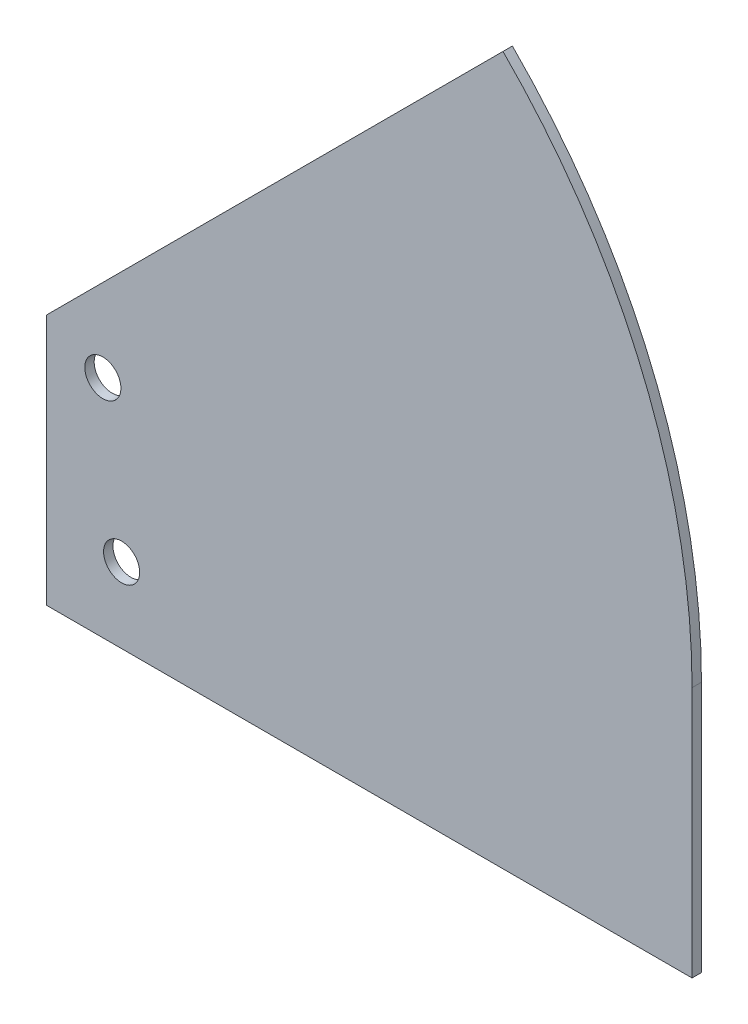
SolidWorks part; units mm, degrees
ref_plane "Front Plane" through (0, 0, 0) normal (0, 0, 1) x (1, 0, 0)
ref_plane "Top Plane" through (0, 0, 0) normal (0, 1, 0) x (1, 0, 0)
ref_plane "Right Plane" through (0, 0, 0) normal (1, 0, 0) x (0, 0, -1)
sketch "Sketch1" plane through (0, 0, 0) normal (0, 0, 1) x (1, 0, 0)
  line L0 (0, 0) -> (218.44, 0)
  line L2 (0, 85.09) -> (0, 0)
  line L3 (19.05, 76.2) -> (69.85, 76.2) construction
  line L4 (218.44, 0) -> (218.44, 85.09)
  line L7 (154.4604, 239.5504) -> (0, 85.09)
  line L8 (0, 85.09) -> (218.44, 85.09) construction
  line L9 (0, 303.53) -> (0, 85.09) construction
  circle A1 centre (19.05, 76.2) radius 6.1087
  circle A3 centre (19.05, 76.2) radius 50.8 construction
  arc A6 (0, 303.53) -> (154.4604, 239.5504) centre (0, 85.09) cw construction
  arc A7 (154.4604, 239.5504) -> (218.44, 85.09) centre (0, 85.09) cw
  point P3 (0, 303.53)
  point P4 (0, 0)
  dimension "D1" = 76.2
  dimension "D2" = 12.2174
  dimension "D6" = 85.09
  dimension "D7" = 101.6
  dimension "D3" = 19.05
  dimension "D4" = 50.8
  dimension "D5" = 218.44
  dimension "D8" = 45
extrude "Boss-Extrude1" add sketch "Sketch1" along normal blind 3.175
sketch "Sketch2" plane through (0, 0, 3.175) normal (0, 0, 1) x (1, 0, 0)
  line L0 (0, 85.09) -> (0, 0) construction
  line L1 (0, 0) -> (218.44, 0) construction
  circle A0 centre (25.4, 25.4) radius 6.1087
  circle A1 centre (19.05, 76.2) radius 50.8
  circle A2 centre (19.05, 76.2) radius 6.1087 construction
  point P2 (47.405, 13.6896)
  point P3 (0, 0)
  point P7 (29.8309, 28.1309)
  dimension "D1" = 101.6
  dimension "D2" = 25.4
  dimension "D3" = 25.4
extrude "Cut-Extrude1" cut sketch "Sketch2" against normal blind 3.175 contours A1 A0 | A0 A1 region at (25.6871, 23.1032, 3.175) region at (25.0437, 28.2504, 3.175)
